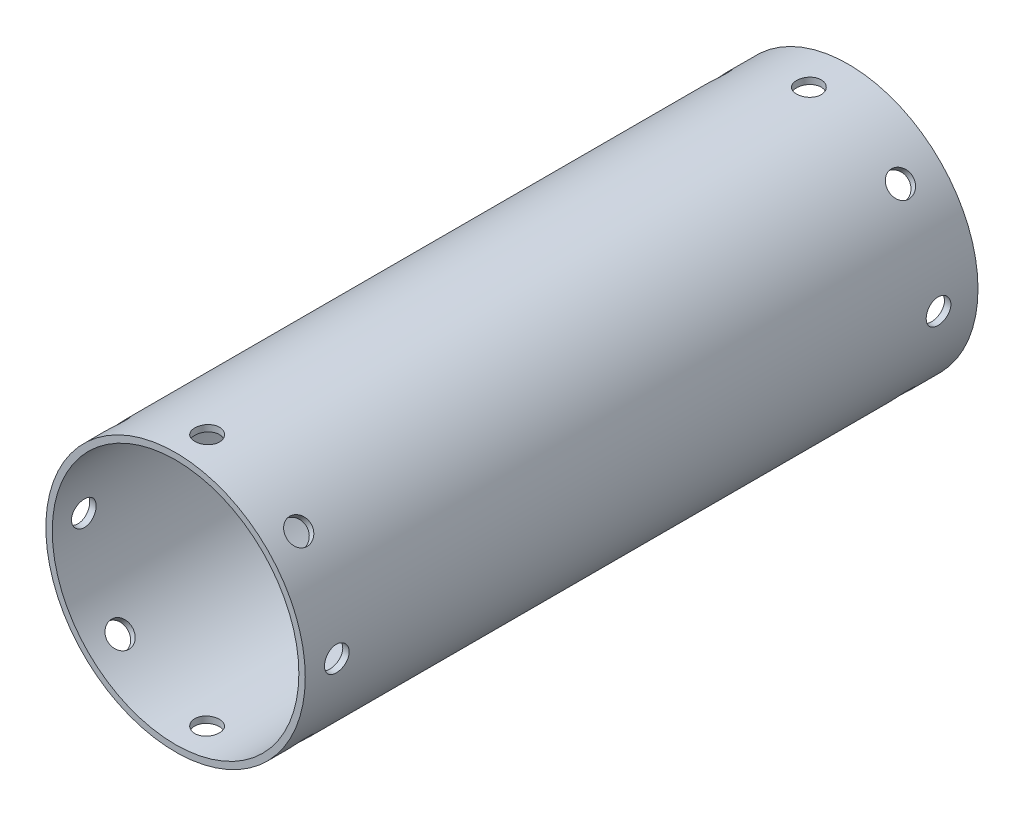
SolidWorks part; units mm, degrees
material "6061-T6 (SS)"
ref_plane "Front Plane" through (0, 0, 0) normal (0, 0, 1) x (1, 0, 0)
ref_plane "Top Plane" through (0, 0, 0) normal (0, 1, 0) x (1, 0, 0)
ref_plane "Right Plane" through (0, 0, 0) normal (1, 0, 0) x (0, 0, -1)
sketch "Sketch1" plane through (0, 0, 0) normal (0, 0, 1) x (1, 0, 0)
  circle A0 centre (0, 0) radius 33.401
  circle A1 centre (0, 0) radius 31.75
  dimension "D1" = 66.802
  dimension "D2" = 63.5
extrude "Boss-Extrude1" add sketch "Sketch1" along normal blind 173.228
sketch "Sketch2" plane through (0, 0, 0) normal (0, 1, 0) x (1, 0, 0)
  line L0 (33.401, 0) -> (-33.401, 0) construction
  circle A0 centre (0, -10.16) radius 3.175
  dimension "D1" = 6.35
  dimension "D2" = 10.16
extrude "Cut-Extrude1" cut sketch "Sketch2" against normal up to next and the other way blind 1
sketch "Sketch3" plane through (0, 0, 0) normal (0, 1, 0) x (1, 0, 0)
  line L0 (0, -149.7653) -> (0, 20.6247) construction
pattern_linear "LPattern1" count 2 spacing 154.94 along (0, 0, 1) of "Cut-Extrude1"
pattern_circular "CirPattern2" count 8 over 360 about axis through (0, 0, 173.228) along (0, 0, -1) of "LPattern1"
sketch3d "3DSketch1"
  line L0 (0, 0, 6.985) -> (0, 0, 13.335) construction
  line L1 (0, 0, 149.7653) -> (0, 0, -20.6247) construction
  line L2 (0, -44.6193, 10.16) -> (0, 44.6193, 10.16) construction
  circle A0 centre (0, 0, 10.16) radius 3.175 construction
  point P4 (0, 3.175, 10.16)
  point P11 (0, 0, 10.16)
ref_axis "Axis1" through (0, -44.6193, 10.16) along (0, 1, 0)
